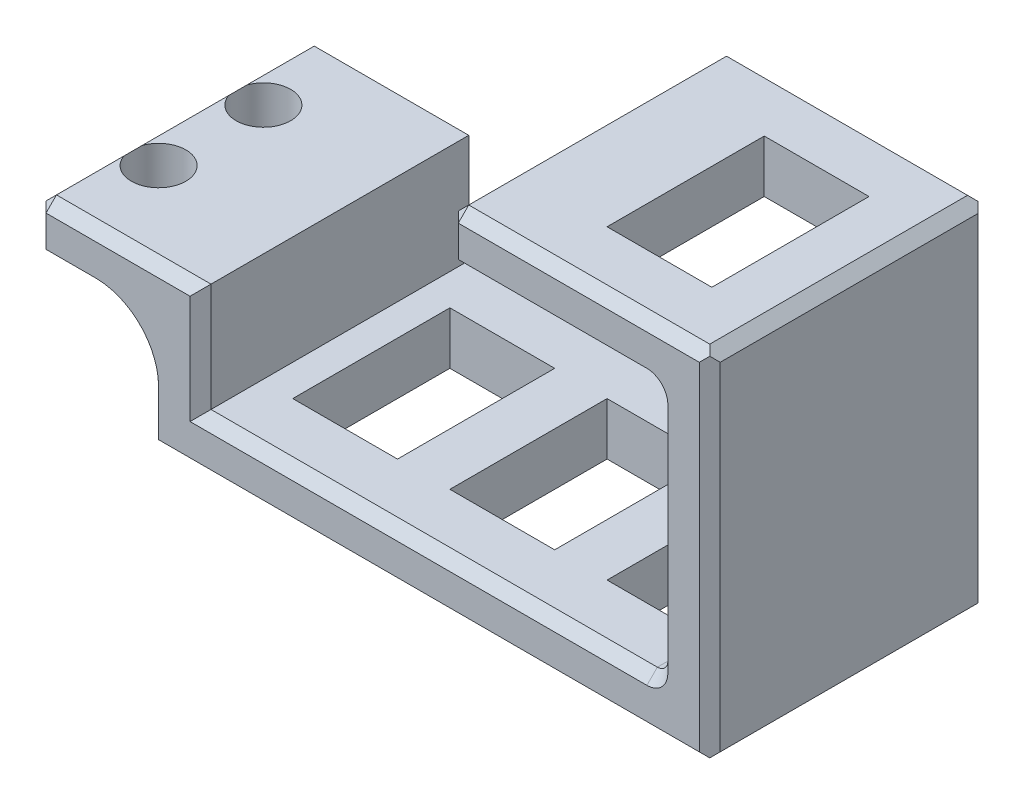
SolidWorks part; units mm, degrees
ref_plane "Alzado" through (0, 0, 0) normal (0, 0, 1) x (1, 0, 0)
ref_plane "Planta" through (0, 0, 0) normal (0, 1, 0) x (1, 0, 0)
ref_plane "Vista lateral" through (0, 0, 0) normal (1, 0, 0) x (0, 0, -1)
sketch "Croquis1" plane through (0, 0, 0) normal (0, 0, 1) x (1, 0, 0)
  line L1 (20.8029, -8) -> (36.55, -8)
  line L2 (20.8029, -8) -> (20.8029, -13)
  line L3 (20.8029, -13) -> (31.55, -13)
  line L6 (80.15, -18.36) -> (85.15, -18.36) construction
  line L8 (31.55, -13) -> (31.55, -23.36)
  line L9 (31.55, -23.36) -> (36.55, -23.36)
  line L10 (36.55, -8) -> (36.55, -18.36)
  line L12 (36.55, -23.36) -> (85.15, -23.36)
  line L14 (36.55, -18.36) -> (80.15, -18.36)
  line L15 (85.15, -23.36) -> (85.15, -18.36)
  line L17 (85.15, -18.36) -> (85.15, 10.84)
  line L18 (85.15, 10.84) -> (80.15, 10.84)
  line L19 (80.15, -18.36) -> (80.15, 5.84)
  line L20 (31.55, -13) -> (36.55, -13) construction
  line L21 (36.55, -23.36) -> (36.55, -18.36) construction
  line L24 (80.15, 10.84) -> (60.15, 10.84)
  line L26 (80.15, 5.84) -> (60.15, 5.84)
  line L27 (60.15, 10.84) -> (60.15, 5.84)
  line L29 (80.15, 10.84) -> (80.15, 5.84) construction
  line L31 (46.55, 5.64) -> (70.15, 5.64) construction
  line L32 (34.55, -8) -> (0, -8) construction
  line L33 (20.6029, -25.5) -> (20.6029, 2.44) construction
  line L34 (36.55, -13.36) -> (36.55, 0.64) construction
  line L35 (41.55, -18.36) -> (46.55, -18.36) construction
  line L36 (80.15, 0.64) -> (80.15, -13.36) construction
  point P4 (20.05, -8)
  point P5 (0, 0)
  point P17 (21.115, -8)
  point P26 (36.55, -13.36)
  point P27 (20.05, -8)
  point P28 (0, 0)
  point P29 (0, 0)
  point P31 (0, 0)
  point P37 (36.55, 8.2732)
  dimension "D1" = 5
  dimension "D2" = 0.2
  dimension "D3" = 0.2
  dimension "D4" = 5
  dimension "D5" = 20
extrude "Saliente-Extruir1" add sketch "Croquis1" against normal up to surface (26.6 mm away) contours L19 L14 L10 L1 L2 L3 L8 L9 L12 L15 L17 L18 region at (28.6764, -8.7287, 0)
sketch "Croquis2" plane through (0, -8, 0) normal (0, 1, 0) x (1, 0, 0)
  circle A0 centre (24.25, 18.3) radius 2.6
  circle A1 centre (24.25, 8.3) radius 2.6
  arc A2 (26.1286, 9.6269) -> (26.1286, 6.9731) centre (24.25, 8.3) ccw construction
  arc A3 (26.1286, 19.6269) -> (26.1286, 16.9731) centre (24.25, 18.3) ccw construction
  dimension "D1" = 0.3
  dimension "D2" = 0.3
extrude "Cortar-Extruir1" cut sketch "Croquis2" against normal through all
fillet "Redondeo1" radius 5 1 edges at (31.55, -13, -13.3)
fillet "Redondeo2" radius 1 2 edges at (80.15, -18.36, -13.3) (80.15, 5.84, -13.3)
chamfer "Chaflán1" distance 1 angle 45 34 edges at (85.15, -6.26, 0) (58.35, -23.36, 0) (31.55, -20.68, 0) (30.0855, -14.4645, 0) (23.6764, -13, 0) (20.8029, -10.5, 0) (28.6764, -8, 0) (57.85, -18.36, 0) (79.8571, -18.0671, 0) (80.15, -6.26, 0) (79.8571, 5.5471, 0) (69.65, 5.84, 0) (60.15, 8.34, 0) (72.65, 10.84, 0) (60.15, 8.34, -26.6) (60.15, 5.84, -13.3) (69.65, 5.84, -26.6) (79.8571, 5.5471, -26.6) (80.15, -6.26, -26.6) (79.8571, -18.0671, -26.6) (57.85, -18.36, -26.6) (28.6764, -8, -26.6) (20.8029, -8, -13.3) (20.8029, -10.5, -26.6) (60.15, 10.84, -13.3) (72.65, 10.84, -26.6) (85.15, -6.26, -26.6) (58.35, -23.36, -26.6) (31.55, -20.68, -26.6) (30.0855, -14.4645, -26.6) (23.6764, -13, -26.6) (20.8029, -13, -13.3) (36.55, -13.18, 0) (36.55, -13.18, -26.6)
sketch "Croquis3" plane through (0, -23.36, 0) normal (0, -1, 0) x (1, 0, 0)
  line L0 (31.55, -13.3) -> (85.15, -13.3) construction
  line L1 (31.55, -25.6) -> (31.55, -1) construction
  line L2 (85.15, -25.6) -> (85.15, -1) construction
  line L3 (64.55, -20.8) -> (64.55, -5.8)
  line L4 (39.55, -20.8) -> (49.55, -20.8)
  line L5 (39.55, -20.8) -> (39.55, -5.8)
  line L6 (39.55, -5.8) -> (49.55, -5.8)
  line L7 (49.55, -20.8) -> (49.55, -5.8)
  line L8 (39.55, -20.8) -> (49.55, -5.8) construction
  line L9 (39.55, -5.8) -> (49.55, -20.8) construction
  line L10 (54.55, -20.8) -> (64.55, -20.8)
  line L11 (54.55, -20.8) -> (54.55, -5.8)
  line L12 (54.55, -5.8) -> (64.55, -5.8)
  line L13 (79.55, -20.8) -> (79.55, -5.8)
  line L14 (69.55, -20.8) -> (79.55, -20.8)
  line L15 (69.55, -20.8) -> (69.55, -5.8)
  line L16 (69.55, -5.8) -> (79.55, -5.8)
  point P6 (44.55, -13.3)
  dimension "D1" = 10
  dimension "D2" = 15
  dimension "D3" = 8
  dimension "D4" = 3
extrude "Cortar-Extruir2" cut sketch "Croquis3" against normal up to next
sketch "Croquis4" plane through (0, -23.36, 0) normal (0, -1, 0) x (1, 0, 0)
  line L0 (79.55, -20.8) -> (79.55, -5.8) construction
  line L1 (69.55, -20.8) -> (79.55, -20.8) construction
  line L2 (79.55, -5.8) -> (69.55, -5.8) construction
  line L3 (69.55, -5.8) -> (69.55, -20.8) construction
  line L4 (79.55, -20.8) -> (79.55, -5.8)
  line L5 (69.55, -20.8) -> (79.55, -20.8)
  line L6 (79.55, -5.8) -> (69.55, -5.8)
  line L7 (69.55, -5.8) -> (69.55, -20.8)
extrude "Cortar-Extruir3" cut sketch "Croquis4" against normal through all
chamfer "Chaflán2" distance 1 angle 45 2 edges at (85.15, 10.84, -13.3) (85.15, -23.36, -13.3)
